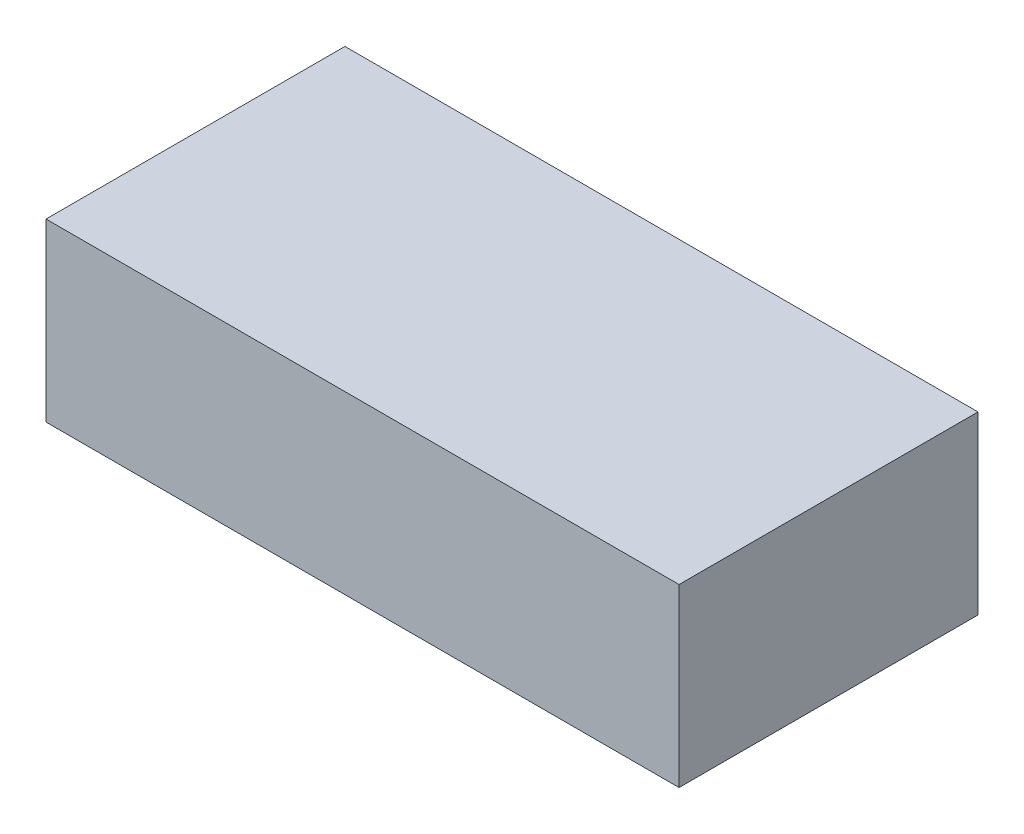
SolidWorks part; units mm, degrees
ref_plane "Front Plane" through (0, 0, 0) normal (0, 0, 1) x (1, 0, 0)
ref_plane "Top Plane" through (0, 0, 0) normal (0, 1, 0) x (1, 0, 0)
ref_plane "Right Plane" through (0, 0, 0) normal (1, 0, 0) x (0, 0, -1)
sketch "Sketch1" plane through (0, 0, 0) normal (0, 0, 1) x (1, 0, 0)
  line L0 (-117.4073, -163.594) -> (-117.4058, 6.406) construction
  line L1 (-117.4067, -97.7573) -> (-81.4066, -97.7573)
  line L2 (-117.4067, -97.7573) -> (-117.4067, -87.7573)
  line L3 (-117.4067, -87.7573) -> (-81.4066, -87.7573)
  line L4 (-81.4066, -97.7573) -> (-81.4066, -87.7573)
  line L5 (-81.4058, 6.4057) -> (-81.4073, -163.5943) construction
  line L6 (-17, -177.7573) -> (-183, -177.7573) construction
  dimension "D1" = 10
  dimension "D2" = 80
extrude "Boss-Extrude1" add sketch "Sketch1" along normal blind 17
